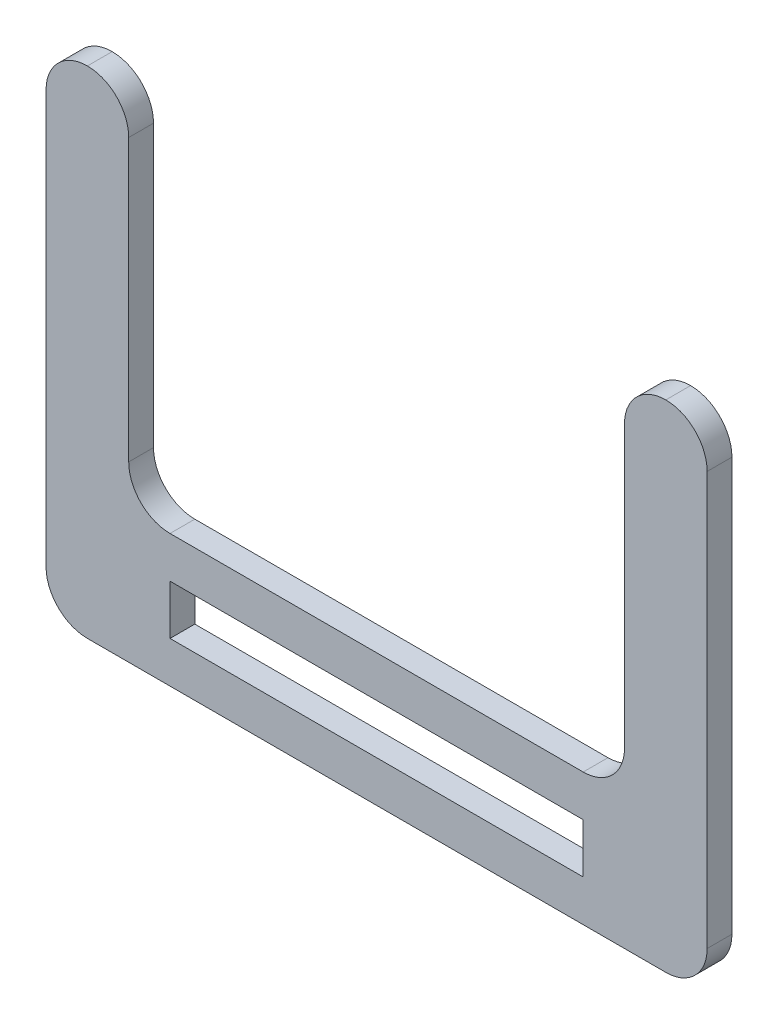
SolidWorks part; units mm, degrees
ref_plane "Plan de face" through (0, 0, 0) normal (0, 0, 1) x (1, 0, 0)
ref_plane "Plan de dessus" through (0, 0, 0) normal (0, 1, 0) x (1, 0, 0)
ref_plane "Plan de droite" through (0, 0, 0) normal (1, 0, 0) x (0, 0, -1)
sketch "Esquisse1" plane through (0, 0, 0) normal (0, 0, 1) x (1, 0, 0)
  line L0 (-63.8455, 55.4954) -> (-53.8455, 55.4954)
  line L2 (-63.8455, -4.5046) -> (-63.8455, 55.4954)
  line L3 (-63.8455, -4.5046) -> (16.1545, -4.5046)
  line L4 (-53.8455, 55.4954) -> (-53.8455, 11.4954)
  line L5 (16.1545, 55.4954) -> (16.1545, -4.5046)
  line L7 (-53.8455, 11.4954) -> (6.1545, 11.4954)
  line L10 (6.1545, 11.4954) -> (6.1545, 55.4954)
  line L11 (6.1545, 55.4954) -> (16.1545, 55.4954)
  dimension "D1" = 10
  dimension "D2" = 60
  dimension "D4" = 80
  dimension "D5" = 10
extrude "Extrusion1" add sketch "Esquisse1" along normal blind 3
sketch "Esquisse2" plane through (0, 0, 3) normal (0, 0, 1) x (1, 0, 0)
  line L0 (-63.8455, -4.5046) -> (16.1545, -4.5046) construction
  line L1 (-48.8455, 6.4954) -> (1.1545, 6.4954)
  line L2 (-48.8455, 6.4954) -> (-48.8455, 0.4954)
  line L3 (-48.8455, 0.4954) -> (1.1545, 0.4954)
  line L4 (1.1545, 6.4954) -> (1.1545, 0.4954)
  line L5 (-63.8455, 55.4954) -> (-63.8455, -4.5046) construction
  dimension "D1" = 5
  dimension "D2" = 6
  dimension "D3" = 15
  dimension "D4" = 50
extrude "Enlèv. mat.-Extru.1" cut sketch "Esquisse2" against normal blind 6
fillet "Congé1" radius 5 8 edges at (-53.8455, 11.4954, 1.5) (6.1545, 11.4954, 1.5) (16.1545, 55.4954, 1.5) (6.1545, 55.4954, 1.5) (-53.8455, 55.4954, 1.5) (-63.8455, 55.4954, 1.5) (16.1545, -4.5046, 1.5) (-63.8455, -4.5046, 1.5)
